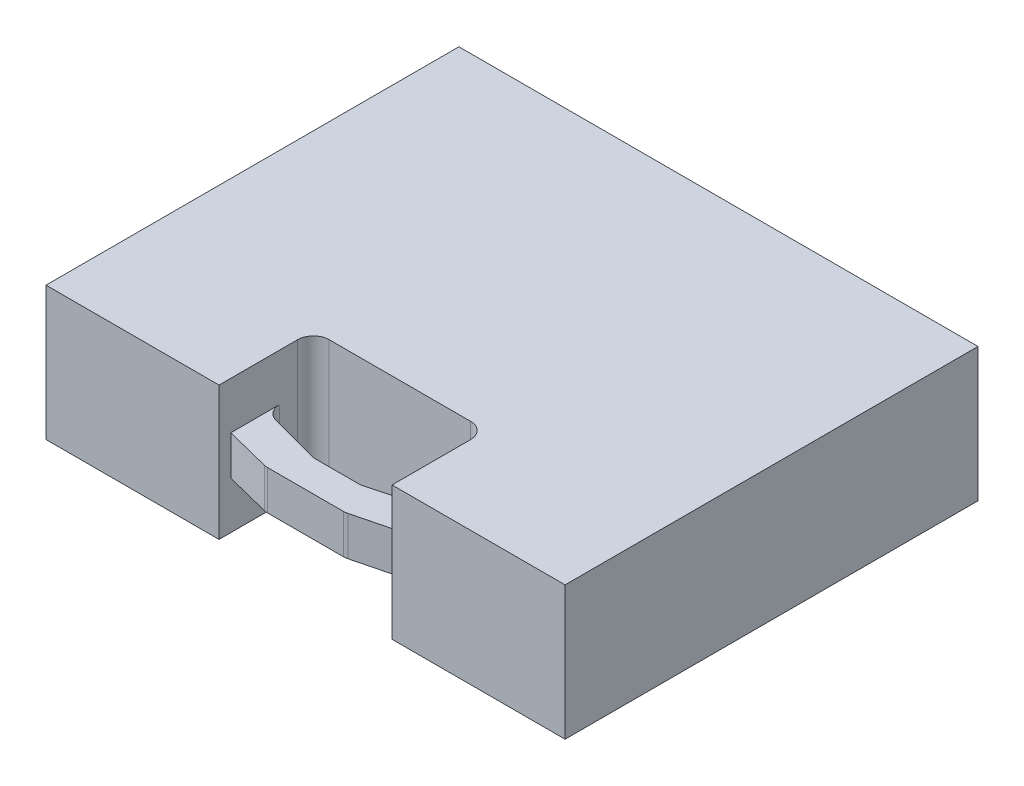
SolidWorks part; units mm, degrees
ref_plane "Front Plane" through (0, 0, 0) normal (0, 0, 1) x (1, 0, 0)
ref_plane "Top Plane" through (0, 0, 0) normal (0, 1, 0) x (1, 0, 0)
ref_plane "Right Plane" through (0, 0, 0) normal (1, 0, 0) x (0, 0, -1)
sketch "Sketch1" plane through (0, 0, 0) normal (0, 1, 0) x (1, 0, 0)
  line L1 (-209.55, -166.6875) -> (209.55, -166.6875)
  line L2 (-209.55, -166.6875) -> (-209.55, 166.6875)
  line L3 (-209.55, 166.6875) -> (209.55, 166.6875)
  line L4 (209.55, -166.6875) -> (209.55, 166.6875)
  line L5 (-209.55, -166.6875) -> (209.55, 166.6875) construction
  line L6 (-209.55, 166.6875) -> (209.55, -166.6875) construction
  point P0 (0, 0)
  dimension "D1" = 333.375
  dimension "D2" = 419.1
extrude "Boss-Extrude1" add sketch "Sketch1" along normal blind 107.95
sketch "Sketch2" plane through (0, 107.95, 0) normal (0, 1, 0) x (1, 0, 0)
  line L0 (0, 0) -> (0, -115.8875) construction
  line L1 (-69.85, -141.2875) -> (69.85, -141.2875)
  line L2 (-69.85, -141.2875) -> (-69.85, -90.4875)
  line L3 (-69.85, -90.4875) -> (69.85, -90.4875)
  line L4 (69.85, -141.2875) -> (69.85, -90.4875)
  line L5 (-69.85, -141.2875) -> (69.85, -90.4875) construction
  line L6 (-69.85, -90.4875) -> (69.85, -141.2875) construction
  line L7 (-209.55, -166.6875) -> (209.55, -166.6875) construction
  line L8 (-69.85, -166.6875) -> (-69.85, -157.1625)
  line L9 (-69.85, -157.1625) -> (-32.169, -166.6875)
  line L10 (-32.169, -166.6875) -> (-69.85, -166.6875)
  line L11 (-69.85, -157.1625) -> (-69.85, -141.2875) construction
  line L12 (0, -166.6875) -> (0, -141.2875) construction
  line L13 (69.85, -157.1625) -> (69.85, -141.2875) construction
  line L14 (32.169, -166.6875) -> (69.85, -166.6875)
  line L15 (69.85, -157.1625) -> (32.169, -166.6875)
  line L16 (69.85, -166.6875) -> (69.85, -157.1625)
  point P0 (0, -115.8875)
  dimension "D1" = 139.7
  dimension "D2" = 50.8
  dimension "D3" = 50.8
  dimension "D4" = 9.525
extrude "Cut-Extrude1" cut sketch "Sketch2" against normal through all
chamfer "Chamfer1" distance 50.8 angle 15 2 edges at (69.85, 53.975, 141.2875) (-69.85, 53.975, 141.2875) first distance on face at (0, 53.975, 141.2875)
fillet "Fillet1" radius 12.7 8 edges at (32.169, 53.975, 166.6875) (-32.169, 53.975, 166.6875) (69.85, 53.975, 127.6757) (19.05, 53.975, 141.2875) (-19.05, 53.975, 141.2875) (-69.85, 53.975, 127.6757) (69.85, 53.975, 90.4875) (-69.85, 53.975, 90.4875)
sketch "Sketch3" plane through (0, 107.95, 0) normal (0, 1, 0) x (1, 0, 0)
  line L1 (-69.85, -166.6875) -> (69.85, -166.6875)
  line L2 (-69.85, -166.6875) -> (-69.85, -110.2845)
  line L3 (-69.85, -110.2845) -> (69.85, -110.2845)
  line L4 (69.85, -166.6875) -> (69.85, -110.2845)
extrude "Cut-Extrude2" cut sketch "Sketch3" against normal blind 38.1
sketch "Sketch4" plane through (0, 0, 0) normal (0, -1, 0) x (1, 0, 0)
  line L0 (69.85, 117.9306) -> (69.85, 103.1875) construction
  line L1 (-69.85, 166.6875) -> (69.85, 166.6875)
  line L2 (-69.85, 166.6875) -> (-69.85, 110.5591)
  line L3 (-69.85, 110.5591) -> (69.85, 110.5591)
  line L4 (69.85, 166.6875) -> (69.85, 110.5591)
extrude "Cut-Extrude3" cut sketch "Sketch4" against normal blind 38.1
